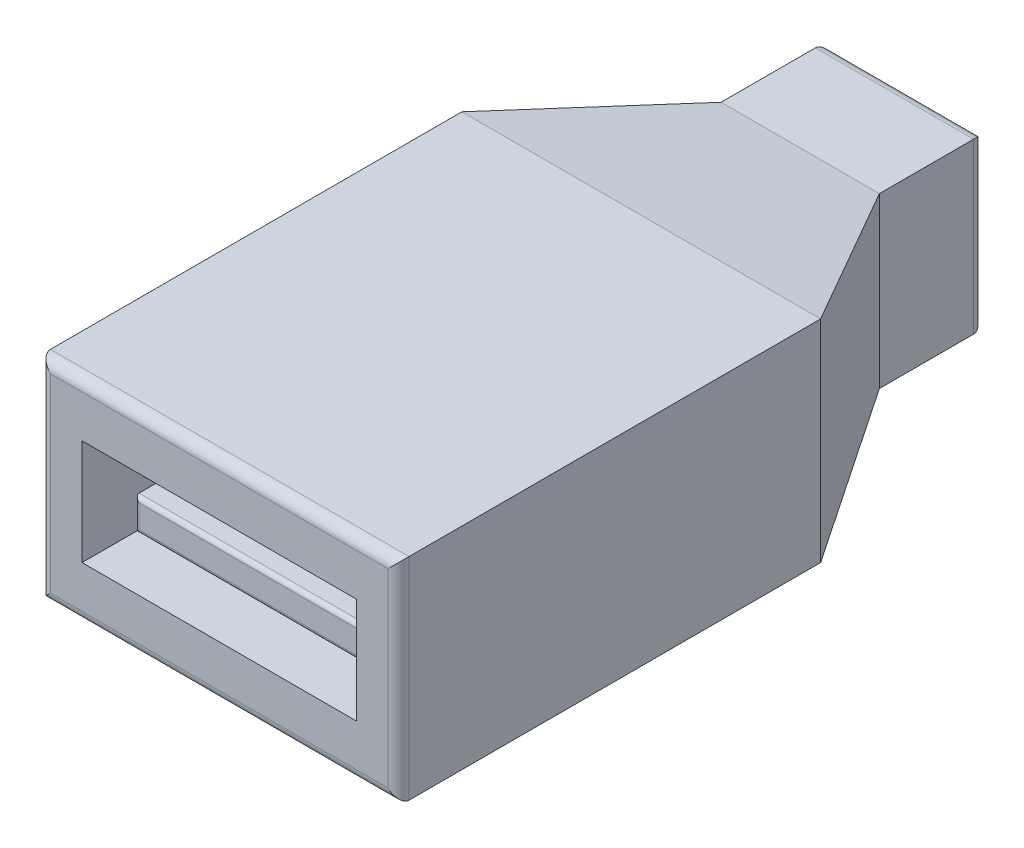
SolidWorks part; units mm, degrees
ref_plane "前视基准面" through (0, 0, 0) normal (0, 0, 1) x (1, 0, 0)
ref_plane "上视基准面" through (0, 0, 0) normal (0, 1, 0) x (1, 0, 0)
ref_plane "右视基准面" through (0, 0, 0) normal (1, 0, 0) x (0, 0, -1)
sketch "草图2" plane through (0, 0, 0) normal (1, 0, 0) x (0, 0, -1)
  line L0 (0, -5) -> (0, 5)
  line L1 (0, 5) -> (20, 5)
  line L2 (20, 5) -> (27.5329, 4)
  line L3 (27.5329, 4) -> (32.5, 4)
  line L4 (32.5, 4) -> (32.5, -4)
  line L5 (-20.6891, 0) -> (45.7935, 0) construction
  line L6 (27.5329, -4) -> (32.5, -4)
  line L7 (20, -5) -> (27.5329, -4)
  line L8 (0, -5) -> (20, -5)
  point P10 (32.5, 0)
  point P13 (0, 0)
  dimension "D1" = 10
  dimension "D2" = 20
  dimension "D3" = 32.5
  dimension "D4" = 8
extrude "凸台-拉伸1" add sketch "草图2" along normal blind 8.5 and the other way blind 8.5
sketch "草图5" plane through (0, 5, 0) normal (0, 1, 0) x (1, 0, 0)
  line L0 (0, -3.1682) -> (0, 35.8515) construction
  line L1 (-3.75, 32.5) -> (-3.75, 27.5329)
  line L2 (-8.5, 32.5) -> (8.5, 32.5) construction
  line L3 (-3.75, 27.5329) -> (-8.5, 20)
  line L4 (-8.5, 20) -> (-8.5, 32.5)
  line L6 (-8.5, 32.5) -> (-3.75, 32.5)
  line L7 (8.5, 32.5) -> (3.75, 32.5)
  line L8 (8.5, 20) -> (8.5, 32.5)
  line L10 (3.75, 27.5329) -> (8.5, 20)
  line L11 (3.75, 32.5) -> (3.75, 27.5329)
  point P12 (0, 32.5)
  dimension "D1" = 7.5
extrude "切除-拉伸3" cut sketch "草图5" against normal through all
fillet "圆角3" radius 0.5 8 edges at (0, 4, -32.5) (-3.75, 0, -32.5) (0, -4, -32.5) (3.75, 0, -32.5) (-8.5, 0, 0) (0, 5, 0) (8.5, 0, 0) (0, -5, 0)
sketch "草图3" plane through (0, 0, 0) normal (0, 0, 1) x (1, 0, 0)
  line L0 (-11.5079, 0) -> (14.0927, 0) construction
  line L1 (-6.5, 2.5) -> (6.5, 2.5)
  line L2 (-6.5, 2.5) -> (-6.5, -2.5)
  line L3 (-6.5, -2.5) -> (6.5, -2.5)
  line L4 (6.5, 2.5) -> (6.5, -2.5)
  line L5 (0, 7.656) -> (0, -7.3646) construction
  dimension "D1" = 13
  dimension "D2" = 5
extrude "切除-拉伸1" cut sketch "草图3" against normal blind 15
sketch "草图4" plane through (0, 0, -15) normal (0, 0, 1) x (1, 0, 0)
  line L0 (0, 2.1835) -> (0, -3.5818) construction
  line L1 (-6, -0.5) -> (6, -0.5)
  line L2 (-6, -0.5) -> (-6, -2)
  line L3 (-6, -2) -> (6, -2)
  line L4 (6, -0.5) -> (6, -2)
  dimension "D1" = 1.5
  dimension "D2" = 0.5
  dimension "D3" = 12
extrude "凸台-拉伸2" add sketch "草图4" along normal offset from surface (13 mm away) 2 up to face at (0, 0, 0)
fillet "圆角2" radius 0.2 4 edges at (6, -1.25, -2) (0, -2, -2) (-6, -1.25, -2) (0, -0.5, -2)
